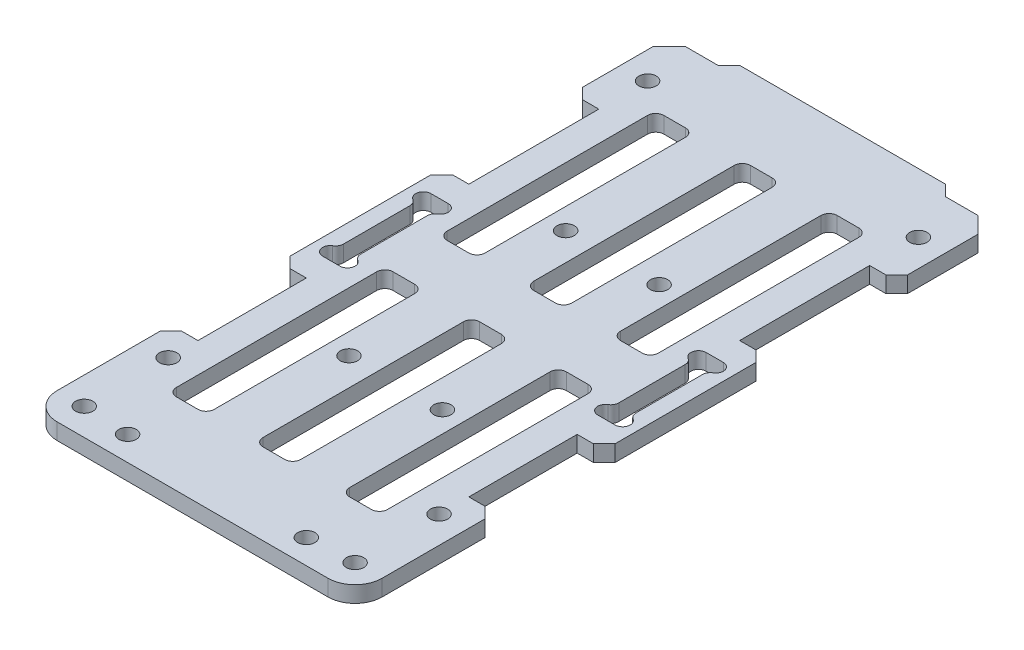
SolidWorks part; units mm, degrees
material "Thornel Mat VMA"
ref_plane "前视基准面" through (0, 0, 0) normal (0, 0, 1) x (1, 0, 0)
ref_plane "上视基准面" through (0, 0, 0) normal (0, 1, 0) x (1, 0, 0)
ref_plane "右视基准面" through (0, 0, 0) normal (1, 0, 0) x (0, 0, -1)
sketch "草图1" plane through (0, 0, 0) normal (0, 1, 0) x (1, 0, 0)
  line L1 (30, -60) -> (-30, -60)
  line L2 (30, -60) -> (30, 60)
  line L3 (30, 60) -> (-30, 60)
  line L4 (-30, -60) -> (-30, 60)
  line L5 (30, -60) -> (-30, 60) construction
  line L6 (30, 60) -> (-30, -60) construction
  point P0 (0, 0)
  dimension "D1" = 120
  dimension "D2" = 60
extrude "凸台-拉伸1" add sketch "草图1" along normal blind 3
sketch "草图2" plane through (0, 3, 0) normal (0, 1, 0) x (1, 0, 0)
  line L0 (-30, 0) -> (0, 0) construction
  line L1 (-30, 60) -> (-30, -60) construction
  line L2 (0, 0) -> (0, 60) construction
  line L3 (30, 60) -> (-30, 60) construction
  line L4 (30, 58) -> (21, 58)
  line L5 (-30, 60) -> (-21, 60)
  line L6 (-30, 60) -> (-30, 58)
  line L7 (-30, 58) -> (-21, 58)
  line L8 (-21, 60) -> (-21, 58)
  line L9 (21, 60) -> (21, 58)
  line L10 (30, 60) -> (21, 60)
  line L11 (30, 60) -> (30, 58)
  line L12 (25, -14) -> (25, -34)
  line L13 (-30, 40) -> (-25, 40)
  line L14 (-30, 40) -> (-30, 16)
  line L15 (-30, 16) -> (-25, 16)
  line L16 (-25, 40) -> (-25, 16)
  line L17 (-30, -14) -> (-25, -14)
  line L18 (-30, -14) -> (-30, -34)
  line L19 (-30, -34) -> (-25, -34)
  line L20 (-25, -14) -> (-25, -34)
  line L21 (30, -34) -> (25, -34)
  line L22 (30, -14) -> (30, -34)
  line L23 (30, -14) -> (25, -14)
  line L24 (25, 40) -> (25, 16)
  line L25 (30, 16) -> (25, 16)
  line L26 (30, 40) -> (30, 16)
  line L27 (30, 40) -> (25, 40)
  line L28 (23.8, 11) -> (23.8, -9)
  line L29 (-27, 11) -> (-23.8, 11)
  line L30 (-27, 11) -> (-27, -9)
  line L31 (-27, -9) -> (-23.8, -9)
  line L32 (-23.8, 11) -> (-23.8, -9)
  line L33 (27, -9) -> (23.8, -9)
  line L34 (27, 11) -> (27, -9)
  line L35 (27, 11) -> (23.8, 11)
  circle A0 centre (-25, 49) radius 1.6
  circle A1 centre (-25, -39.5) radius 1.6
  circle A2 centre (25, -39.5) radius 1.6
  circle A3 centre (25, 49) radius 1.6
  dimension "D3" = 3.2
  dimension "D4" = 11
  dimension "D10" = 3.2
  dimension "D1" = 2
  dimension "D2" = 42
  dimension "D5" = 20
  dimension "D6" = 24
  dimension "D7" = 30
  dimension "D8" = 20
  dimension "D9" = 5
  dimension "D11" = 88.5
  dimension "D12" = 50
  dimension "D13" = 3
  dimension "D14" = 3.2
  dimension "D15" = 5
  dimension "D16" = 20
extrude "切除-拉伸1" cut sketch "草图2" against normal blind 10
sketch "草图3" plane through (0, 3, 0) normal (0, 1, 0) x (1, 0, 0)
  line L0 (-23.8, -9) -> (-23.8, 11) construction
  line L1 (-27, 11) -> (-27, -9) construction
  line L2 (0, 0) -> (0, 60) construction
  line L3 (21, 60) -> (-21, 60) construction
  circle A0 centre (-23.8, 9.6) radius 1.4
  circle A1 centre (-27, 9.6) radius 1.4
  circle A2 centre (-27, -7.6) radius 1.4
  circle A3 centre (-23.8, -7.6) radius 1.4
  circle A4 centre (23.8, -7.6) radius 1.4
  circle A5 centre (27, -7.6) radius 1.4
  circle A6 centre (27, 9.6) radius 1.4
  circle A7 centre (23.8, 9.6) radius 1.4
  dimension "D1" = 2.8
  dimension "D2" = 2.8
  dimension "D3" = 2.8
  dimension "D4" = 2.8
extrude "切除-拉伸2" cut sketch "草图3" against normal blind 10
sketch "草图4" plane through (0, 3, 0) normal (0, 1, 0) x (1, 0, 0)
  line L0 (-30, -55) -> (0, -55) construction
  line L1 (-30, -34) -> (-30, -60) construction
  line L2 (0, -55) -> (0, -60) construction
  line L3 (-30, -60) -> (30, -60) construction
  circle A0 centre (-25, -55) radius 1.6
  circle A1 centre (25, -55) radius 1.6
  dimension "D2" = 3.2
  dimension "D3" = 5
  dimension "D1" = 5
extrude "切除-拉伸3" cut sketch "草图4" against normal blind 10
sketch "草图5" plane through (0, 3, 0) normal (0, 1, 0) x (1, 0, 0)
  line L1 (-30, -60) -> (30, -60) construction
  line L6 (0, 0) -> (0, 60) construction
  line L7 (8.625, -22.5) -> (-8.625, -22.5) construction
  line L8 (8.625, -22.5) -> (8.625, 17.5) construction
  line L9 (8.625, 17.5) -> (-8.625, 17.5) construction
  line L10 (-8.625, -22.5) -> (-8.625, 17.5) construction
  line L11 (8.625, -22.5) -> (-8.625, 17.5) construction
  line L12 (8.625, 17.5) -> (-8.625, -22.5) construction
  line L13 (21, 60) -> (-21, 60) construction
  circle A0 centre (-8.625, -22.5) radius 1.6
  circle A1 centre (8.625, -22.5) radius 1.6
  circle A2 centre (8.625, 17.5) radius 1.6
  circle A3 centre (-8.625, 17.5) radius 1.6
  circle A4 centre (-16.5, -55.5) radius 1.6
  circle A5 centre (16.5, -55.5) radius 1.6
  point P9 (0, -2.5)
  dimension "D4" = 3.2
  dimension "D9" = 37.5
  dimension "D1" = 33
  dimension "D2" = 4.5
  dimension "D3" = 3.2
  dimension "D5" = 17.25
  dimension "D6" = 40
  dimension "D7" = 2
  dimension "D8" = 2
extrude "切除-拉伸6" cut sketch "草图5" against normal blind 10
chamfer "倒角1" distance 2 angle 45 2 edges at (-21, 1.5, -60) (21, 1.5, -60)
chamfer "倒角2" distance 3 angle 45 2 edges at (-30, 1.5, -58) (30, 1.5, -58)
chamfer "倒角3" distance 2 angle 45 8 edges at (-30, 1.5, 34) (-30, 1.5, 14) (30, 1.5, 34) (30, 1.5, 14) (30, 1.5, -40) (30, 1.5, -16) (-30, 1.5, -16) (-30, 1.5, -40)
fillet "圆角1" radius 5 2 edges at (30, 1.5, 60) (-30, 1.5, 60)
sketch "草图7" plane through (0, 3, 0) normal (0, 1, 0) x (1, 0, 0)
  line L0 (0, 60) -> (0, 0) construction
  line L1 (19, 60) -> (-19, 60) construction
  line L2 (0, 0) -> (30.0167, 0) construction
  line L4 (19.5, 45) -> (19.5, -45)
  line L5 (-3.5, 45) -> (3.5, 45)
  line L6 (-3.5, 45) -> (-3.5, -45)
  line L7 (-3.5, -45) -> (3.5, -45)
  line L8 (3.5, 45) -> (3.5, -45)
  line L9 (-3.5, 45) -> (3.5, -45) construction
  line L10 (-3.5, -45) -> (3.5, 45) construction
  line L11 (12.5, 45) -> (12.5, -45)
  line L12 (12.5, 45) -> (19.5, 45)
  line L13 (12.5, -45) -> (19.5, -45)
  line L14 (-19.5, 45) -> (-19.5, -45)
  line L15 (-12.5, 45) -> (-12.5, -45)
  line L16 (-19.5, 45) -> (-12.5, 45)
  line L17 (-19.5, -45) -> (-12.5, -45)
  point P5 (0, 0)
  dimension "D1" = 90
  dimension "D2" = 7
  dimension "D5" = 9
  dimension "D6" = 9
  dimension "D3" = 2
  dimension "D4" = 2
extrude "切除-拉伸7" cut sketch "草图7" against normal through all
sketch "草图8" plane through (0, 0, 0) normal (0, -1, 0) x (1, 0, 0)
  line L0 (-19.5, -45) -> (-19.5, 45) construction
  line L1 (19.5, -5) -> (-19.5, -5)
  line L2 (19.5, -5) -> (19.5, 5)
  line L3 (19.5, 5) -> (-19.5, 5)
  line L4 (-19.5, -5) -> (-19.5, 5)
  line L5 (19.5, -5) -> (-19.5, 5) construction
  line L6 (19.5, 5) -> (-19.5, -5) construction
  point P0 (0, 0)
  dimension "D1" = 10
extrude "凸台-拉伸3" add sketch "草图8" against normal blind 3
fillet "圆角2" radius 1.5 32 edges at (-27, 1.5, 6.2) (-27, 1.5, -8.2) (-23.8, 1.5, -8.2) (-23.8, 1.5, 6.2) (27, 1.5, -8.2) (27, 1.5, 6.2) (23.8, 1.5, 6.2) (23.8, 1.5, -8.2) (-12.5, 1.5, 45) (-19.5, 1.5, 5) (-12.5, 1.5, 5) (12.5, 1.5, -45) (19.5, 1.5, -45) (19.5, 1.5, -5) (12.5, 1.5, -5) (-19.5, 1.5, -5) (-19.5, 1.5, -45) (-12.5, 1.5, -45) (-12.5, 1.5, -5) (-3.5, 1.5, -5) (-3.5, 1.5, -45) (3.5, 1.5, -45) (3.5, 1.5, -5) (19.5, 1.5, 5) (19.5, 1.5, 45) (12.5, 1.5, 45) (12.5, 1.5, 5) (3.5, 1.5, 5) (3.5, 1.5, 45) (-3.5, 1.5, 45) (-3.5, 1.5, 5) (-19.5, 1.5, 45)
